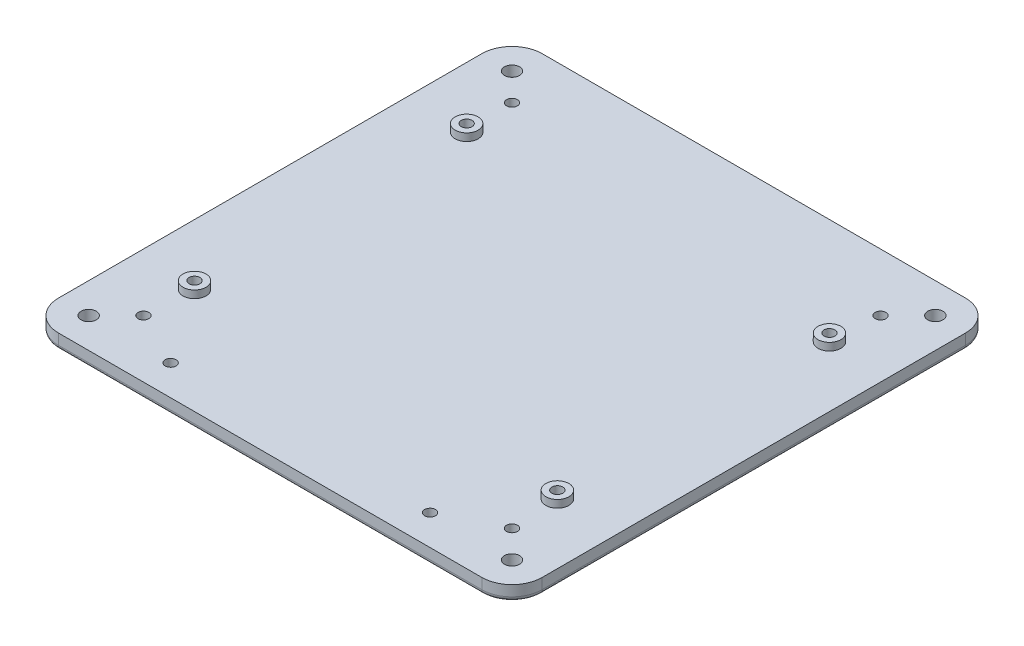
SolidWorks part; units mm, degrees
ref_plane "Front Plane" through (0, 0, 0) normal (0, 0, 1) x (1, 0, 0)
ref_plane "Top Plane" through (0, 0, 0) normal (0, 1, 0) x (1, 0, 0)
ref_plane "Right Plane" through (0, 0, 0) normal (1, 0, 0) x (0, 0, -1)
sketch "Sketch1" plane through (0, 0, 0) normal (0, 1, 0) x (1, 0, 0)
  line L1 (0, 0) -> (203.2, 0)
  line L2 (0, 0) -> (0, 203.2)
  line L3 (0, 203.2) -> (203.2, 203.2)
  line L4 (203.2, 0) -> (203.2, 203.2)
  dimension "D1" = 203.2
  dimension "D2" = 203.2
extrude "Boss-Extrude1" add sketch "Sketch1" along normal blind 6.35
fillet "Fillet1" radius 12.7 4 edges at (0, 3.175, -203.2) (0, 3.175, 0) (203.2, 3.175, 0) (203.2, 3.175, -203.2)
sketch "Sketch2" plane through (0, 0, 0) normal (0, -1, 0) x (1, 0, 0)
  circle A0 centre (12.7, -12.7) radius 3.175
  circle A1 centre (190.5, -12.7) radius 3.175
  circle A2 centre (190.5, -190.5) radius 3.175
  circle A3 centre (12.7, -190.5) radius 3.175
  arc A4 (190.5, -203.2) -> (203.2, -190.5) centre (190.5, -190.5) ccw construction
  arc A5 (12.7, 0) -> (0, -12.7) centre (12.7, -12.7) ccw construction
  arc A6 (12.7, 0) -> (0, -12.7) centre (12.7, -12.7) ccw construction
  dimension "D1" = 6.35
  dimension "D2" = 9.525
extrude "Cut-Extrude1" cut sketch "Sketch2" against normal through all
fillet "Fillet2" radius 1.905 12 edges at (3.7197, 0, -3.7197) (101.6, 0, 0) (199.4803, 0, -3.7197) (203.2, 0, -101.6) (199.4803, 0, -199.4803) (101.6, 0, -203.2) (3.7197, 0, -199.4803) (0, 0, -101.6) (12.7, 0, -15.875) (190.5, 0, -15.875) (190.5, 0, -193.675) (12.7, 0, -193.675)
sketch "Sketch3" plane through (0, 6.35, 0) normal (0, 1, 0) x (1, 0, 0)
  line L0 (3.7197, 3.7197) -> (24.1978, 24.1978) construction
  line L1 (24.1978, 24.1978) -> (0, 24.1978) construction
  line L2 (0, 190.5) -> (0, 12.7) construction
  line L3 (24.1978, 24.1978) -> (24.1978, 0) construction
  line L4 (12.7, 0) -> (190.5, 0) construction
  line L5 (3.7197, 199.4803) -> (24.1978, 179.0022) construction
  line L6 (0, 179.0022) -> (24.1978, 179.0022) construction
  line L7 (24.1978, 179.0022) -> (24.1978, 203.2) construction
  line L8 (190.5, 203.2) -> (12.7, 203.2) construction
  line L9 (199.4803, 3.7197) -> (179.0022, 24.1978) construction
  line L10 (179.0022, 24.1978) -> (179.0022, 0) construction
  line L12 (179.0022, 24.1978) -> (203.2, 24.1978) construction
  line L13 (203.2, 12.7) -> (203.2, 190.5) construction
  line L14 (199.4803, 199.4803) -> (179.0022, 179.0022) construction
  line L15 (179.0022, 179.0022) -> (203.2, 179.0022) construction
  line L16 (179.0022, 179.0022) -> (179.0022, 203.2) construction
  arc A0 (0, 12.7) -> (12.7, 0) centre (12.7, 12.7) ccw construction
  circle A1 centre (24.1978, 24.1978) radius 2.286
  arc A2 (190.5, 0) -> (203.2, 12.7) centre (190.5, 12.7) ccw construction
  arc A3 (203.2, 190.5) -> (190.5, 203.2) centre (190.5, 190.5) ccw construction
  arc A10 (12.7, 203.2) -> (0, 190.5) centre (12.7, 190.5) ccw construction
  circle A13 centre (179.0022, 179.0022) radius 2.286
  circle A14 centre (179.0022, 24.1978) radius 2.286
  circle A15 centre (24.1978, 179.0022) radius 2.286
  point P20 (101.6, 101.6)
  dimension "D2" = 4.572
  dimension "D1" = 28.9603
extrude "Cut-Extrude2" cut sketch "Sketch3" against normal through all
sketch "Sketch4" plane through (0, 6.35, 0) normal (0, 1, 0) x (1, 0, 0)
  line L0 (0, 190.5) -> (0, 12.7) construction
  line L1 (203.2, 12.7) -> (203.2, 190.5) construction
  line L2 (12.7, 0) -> (190.5, 0) construction
  circle A0 centre (47.117, 12.7) radius 2.286
  circle A1 centre (156.083, 12.7) radius 2.286
  dimension "D4" = 4.572
  dimension "D1" = 47.117
  dimension "D2" = 47.117
  dimension "D3" = 12.7
extrude "Cut-Extrude3" cut sketch "Sketch4" against normal through all
sketch "Sketch5" plane through (0, 6.35, 0) normal (0, 1, 0) x (1, 0, 0)
  line L0 (0, 190.5) -> (0, 12.7) construction
  line L1 (203.2, 12.7) -> (203.2, 190.5) construction
  line L2 (12.7, 0) -> (190.5, 0) construction
  line L3 (190.5, 203.2) -> (12.7, 203.2) construction
  circle A0 centre (25.4, 158.75) radius 2.286
  circle A1 centre (177.8, 158.75) radius 2.286
  circle A2 centre (177.8, 44.45) radius 2.286
  circle A3 centre (25.4, 44.45) radius 2.286
  circle A4 centre (25.4, 158.75) radius 4.826
  circle A5 centre (177.8, 158.75) radius 4.826
  circle A6 centre (177.8, 44.45) radius 4.826
  circle A7 centre (25.4, 44.45) radius 4.826
  point P16 (0, 0)
  point P19 (0, 0)
  dimension "D1" = 2.54
  dimension "D2" = 4.572
  dimension "D3" = 25.4
  dimension "D4" = 25.4
  dimension "D5" = 44.45
  dimension "D6" = 44.45
extrude "Boss-Extrude2" add sketch "Sketch5" along normal blind 3.175
